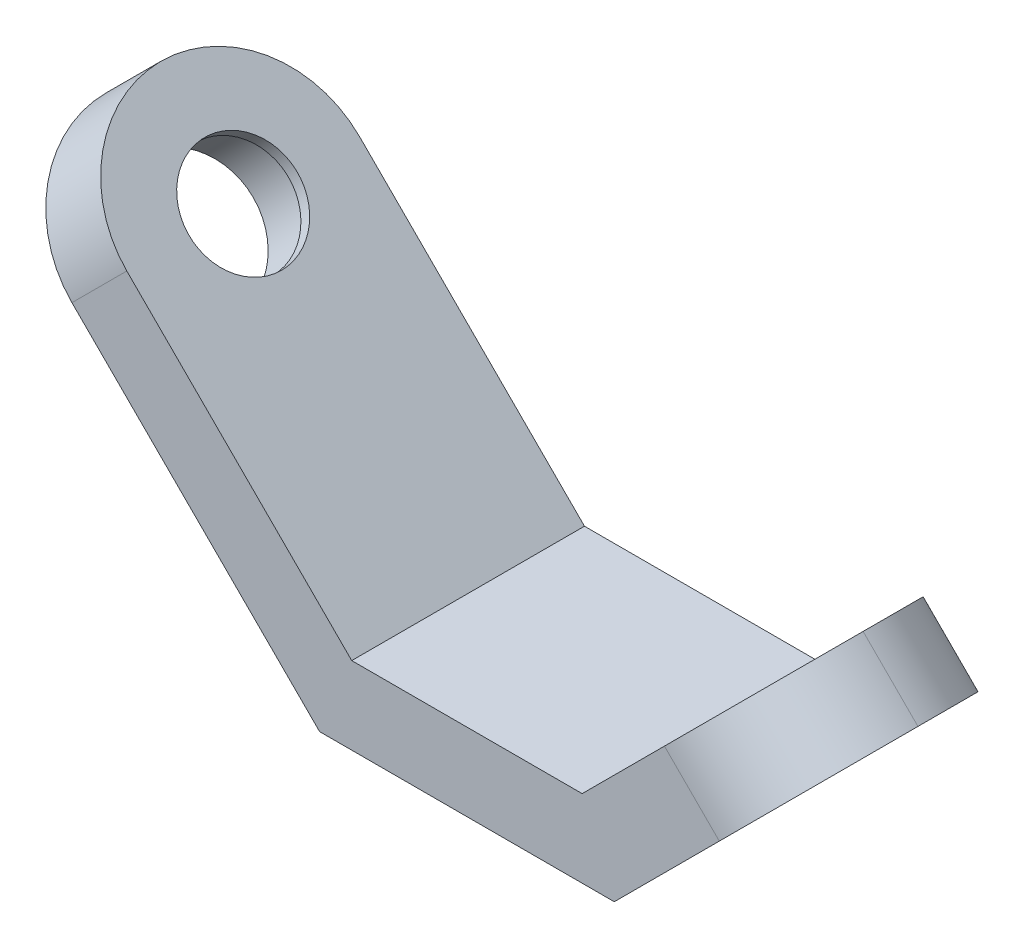
SolidWorks part; units mm, degrees
ref_plane "正面" through (0, 0, 0) normal (0, 0, 1) x (1, 0, 0)
ref_plane "平面" through (0, 0, 0) normal (0, 1, 0) x (1, 0, 0)
ref_plane "右側面" through (0, 0, 0) normal (1, 0, 0) x (0, 0, -1)
sketch "ｽｹｯﾁ1" plane through (0, 0, 0) normal (0, 0, 1) x (1, 0, 0)
  line L0 (0, 0) -> (-21.2635, 21.2635)
  line L1 (-21.2635, 21.2635) -> (-17.7279, 24.799)
  line L2 (-17.7279, 24.799) -> (2.0711, 5)
  line L3 (2.0711, 5) -> (16.9203, 5)
  line L4 (16.9203, 5) -> (27.5269, 15.6066)
  line L5 (27.5269, 15.6066) -> (31.0624, 12.0711)
  line L6 (31.0624, 12.0711) -> (18.9914, 0)
  line L7 (18.9914, 0) -> (0, 0)
  point P6 (-12.4246, 19.4957)
  point P10 (22.2236, 10.3033)
  dimension "D1" = 135
  dimension "D2" = 135
  dimension "D3" = 5
  dimension "D4" = 5
  dimension "D5" = 5
  dimension "D6" = 28
  dimension "D7" = 15
  dimension "D8" = 7.5
  dimension "D9" = 7.5
  dimension "D10" = 18
extrude "ﾎﾞｽ - 押し出し1" add sketch "ｽｹｯﾁ1" along normal mid plane 15
sketch "ｽｹｯﾁ2" plane through (3.5355, 3.5355, 0) normal (-0.7071, -0.7071, 0) x (0, 0, 1)
  line L1 (7.5, 30.0711) -> (-7.5, 30.0711) construction
  circle A0 centre (0, 22.5711) radius 4.2
  dimension "D1" = 8.4
  dimension "D2" = 7.5
extrude "ｶｯﾄ - 押し出し1" cut sketch "ｽｹｯﾁ2" against normal through all both and the other way through all
sketch "ｽｹｯﾁ3" plane through (9.4957, -9.4957, 0) normal (0.7071, -0.7071, 0) x (0, 0, -1)
  line L1 (-7.5, 30.5) -> (7.5, 30.5) construction
  circle A0 centre (0, 23) radius 4.2
  point P7 (0, 30.5)
  dimension "D1" = 8.4
  dimension "D2" = 7.5
extrude "ｶｯﾄ - 押し出し2" cut sketch "ｽｹｯﾁ3" against normal through all both and the other way through all
fillet "ﾌｨﾚｯﾄ1" radius 7.5 4 edges at (29.2947, 13.8388, -7.5) (29.2947, 13.8388, 7.5) (-19.4957, 23.0312, -7.5) (-19.4957, 23.0312, 7.5)
sketch "ｽｹｯﾁ4" plane through (3.5355, 3.5355, 0) normal (-0.7071, -0.7071, 0) x (0, 0, 1)
  circle A0 centre (0, 22.5711) radius 4.2
  circle A1 centre (0, 22.5711) radius 3.5
  circle A2 centre (0, 22.5711) radius 4.2 construction
  dimension "D1" = 7
extrude "ﾎﾞｽ - 押し出し2" add sketch "ｽｹｯﾁ4" along normal blind 0.8
sketch "ｽｹｯﾁ5" plane through (9.4957, -9.4957, 0) normal (-0.7071, 0.7071, 0) x (0, 0, 1)
  circle A0 centre (0, 23) radius 4.2 construction
  circle A1 centre (0, 23) radius 4.2
  circle A2 centre (0, 23) radius 3.5
  dimension "D1" = 7
extrude "ﾎﾞｽ - 押し出し3" add sketch "ｽｹｯﾁ5" along normal blind 0.8
equation "\"D4@ｽｹｯﾁ1\"=\"D3@ｽｹｯﾁ1\""
equation "\"D5@ｽｹｯﾁ1\"=\"D3@ｽｹｯﾁ1\""
